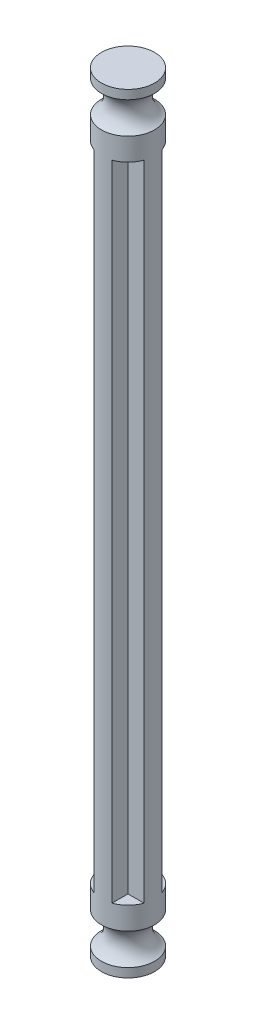
SolidWorks part; units mm, degrees
ref_plane "前视基准面" through (0, 0, 0) normal (0, 0, 1) x (1, 0, 0)
ref_plane "上视基准面" through (0, 0, 0) normal (0, 1, 0) x (1, 0, 0)
ref_plane "右视基准面" through (0, 0, 0) normal (1, 0, 0) x (0, 0, -1)
sketch "草图1" plane through (0, 0, 0) normal (0, 1, 0) x (1, 0, 0)
  line L0 (1, 1) -> (1, 2.7753)
  line L7 (1, 1) -> (2.7753, 1)
  line L8 (1, -1) -> (2.7753, -1)
  line L9 (1, -1) -> (1, -2.7753)
  line L10 (-1, -1) -> (-1, -2.7753)
  line L11 (-1, -1) -> (-2.7753, -1)
  line L12 (-1, 1) -> (-2.7753, 1)
  line L13 (-1, 1) -> (-1, 2.7753)
  arc A0 (-2.7753, 1) -> (-2.7753, -1) centre (0, 0) ccw
  arc A1 (-1, -2.7753) -> (1, -2.7753) centre (0, 0) ccw
  arc A2 (2.7753, -1) -> (2.7753, 1) centre (0, 0) ccw
  arc A3 (1, 2.7753) -> (-1, 2.7753) centre (0, 0) ccw
  dimension "D1" = 5.9
  dimension "D2" = 2
  dimension "D3" = 2
  dimension "D4" = 2
  dimension "D5" = 2
  dimension "D6" = 1
  dimension "D7" = 1
  dimension "D8" = 1
  dimension "D9" = 1
extrude "凸台-拉伸2" add sketch "草图1" along normal blind 71.42
sketch "草图3" plane through (0, 0, 0) normal (1, 0, 0) x (0, 0, -1)
  line L0 (0, 71.42) -> (0, 78.42)
  line L1 (1, 71.42) -> (-1, 71.42) construction
  line L2 (0, 78.42) -> (2.95, 78.42)
  line L3 (0, 71.42) -> (2.95, 71.42)
  line L4 (2.95, 71.42) -> (2.95, 73.92)
  line L5 (2.95, 78.42) -> (2.95, 77.42)
  line L6 (0, 0) -> (0, -7)
  line L7 (0, -7) -> (2.95, -7)
  line L8 (0, 0) -> (2.95, 0)
  line L9 (2.95, 0) -> (2.95, -2.5)
  line L10 (2.95, -7) -> (2.95, -6)
  arc A0 (2.95, 77.42) -> (2.95, 73.92) centre (3.9182, 75.67) ccw
  arc A1 (2.95, -2.5) -> (2.95, -6) centre (3.9182, -4.25) ccw
  dimension "D5" = 1
  dimension "D4" = 2
  dimension "D9" = 2
  dimension "D1" = 2.95
  dimension "D2" = 7
  dimension "D3" = 2.5
  dimension "D6" = 7
  dimension "D7" = 2.5
  dimension "D8" = 1
revolve "旋转3" add sketch "草图3" angle 360 about L6
